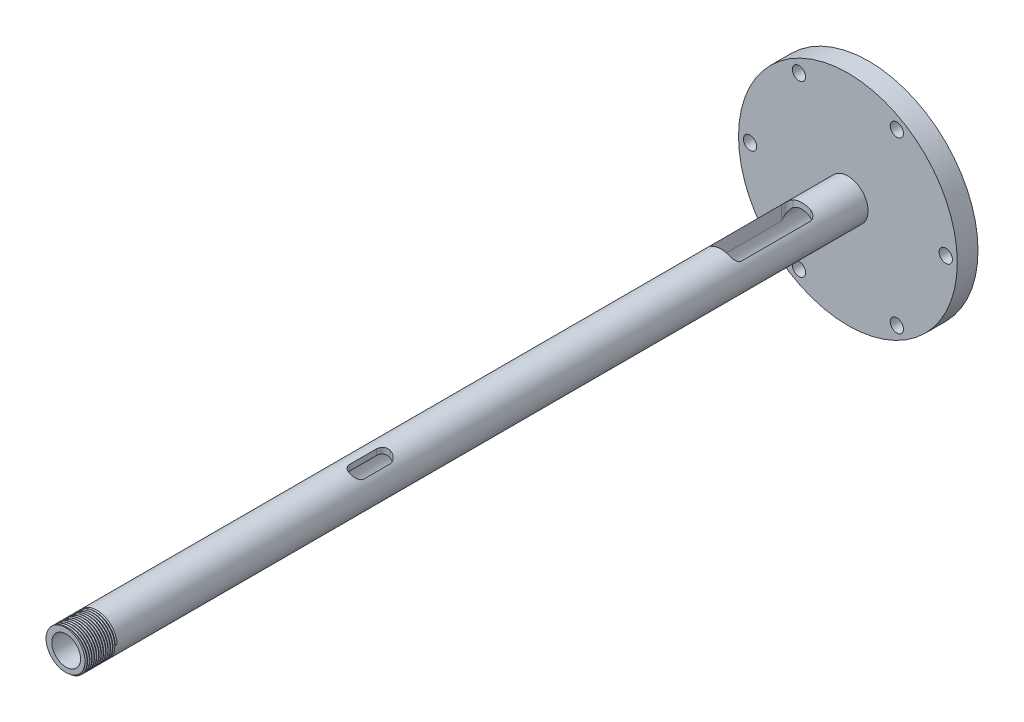
SolidWorks part; units mm, degrees
ref_plane "Front" through (0, 0, 0) normal (0, 0, 1) x (1, 0, 0)
ref_plane "Top" through (0, 0, 0) normal (0, 1, 0) x (1, 0, 0)
ref_plane "Right" through (0, 0, 0) normal (1, 0, 0) x (0, 0, -1)
sketch "Sketch1" plane through (0, 0, 0) normal (0, 0, 1) x (1, 0, 0)
  circle A0 centre (0, 0) radius 17.5
  circle A1 centre (0, 0) radius 12.5
  dimension "D1" = 35
  dimension "D2" = 25
extrude "Boss-Extrude1" add sketch "Sketch1" along normal blind 700
sketch "Sketch2" plane through (0, 0, 0) normal (0, 0, -1) x (-1, 0, 0)
  circle A0 centre (0, 0) radius 72.5
  circle A1 centre (0, 0) radius 12.5 construction
  circle A2 centre (0, 0) radius 12.5
  dimension "D1" = 145
extrude "Boss-Extrude2" add sketch "Sketch2" against normal blind 3
sketch "Sketch3" plane through (0, 0, 3) normal (0, 0, 1) x (1, 0, 0)
  circle A0 centre (0, 0) radius 95
  circle A1 centre (0, 0) radius 17.5 construction
  circle A2 centre (0, 0) radius 17.5
  dimension "D1" = 190
extrude "Boss-Extrude3" add sketch "Sketch3" along normal blind 18
sketch "Sketch4" plane through (0, 0, 3) normal (0, 0, -1) x (-1, 0, 0)
  line L0 (0, 0) -> (85, 0) construction
  circle A0 centre (0, 0) radius 85 construction
  circle A1 centre (85, 0) radius 5.75
  dimension "D1" = 170
  dimension "D2" = 11.5
extrude "Cut-Extrude1" cut sketch "Sketch4" against normal up to next
pattern_circular "CirPattern1" count 6 over 360 about axis through (0, 0, 21) along (0, 0, 1) of "Cut-Extrude1"
sketch "Sketch5" plane through (0, 0, 0) normal (0, 1, 0) x (1, 0, 0)
  line L0 (0, 0) -> (0, -61) construction
  line L1 (-12.5, -61) -> (12.5, -61)
  line L2 (-12.5, -61) -> (-12.5, -131)
  line L3 (-12.5, -131) -> (12.5, -131)
  line L4 (12.5, -61) -> (12.5, -131)
  line L5 (-12.5, -61) -> (12.5, -131) construction
  line L6 (-12.5, -131) -> (12.5, -61) construction
  line L7 (-17.5, -21) -> (17.5, -21) construction
  point P0 (0, -96)
  dimension "D1" = 25
  dimension "D2" = 40
  dimension "D3" = 70
extrude "Cut-Extrude2" cut sketch "Sketch5" along normal up to next
fillet "Fillet1" radius 5 4 edges at (-12.5, 6.1237, 131) (12.5, 6.1237, 131) (12.5, 6.1237, 61) (-12.5, 6.1237, 61)
sketch "Sketch7" plane through (0, 0, 0) normal (0, 1, 0) x (1, 0, 0)
  line L0 (-17.5, -700) -> (17.5, -700) construction
  line L1 (12.5, -460) -> (0.5, -460)
  line L2 (12.5, -460) -> (12.5, -425)
  line L3 (12.5, -425) -> (0.5, -425)
  line L4 (0.5, -460) -> (0.5, -425)
  line L5 (12.5, -460) -> (0.5, -425) construction
  line L6 (12.5, -425) -> (0.5, -460) construction
  line L7 (12.5, -126) -> (12.5, -66) construction
  point P4 (6.5, -442.5)
  dimension "D1" = 240
  dimension "D2" = 35
  dimension "D3" = 12
extrude "Cut-Extrude3" cut sketch "Sketch7" along normal up to next
fillet "Fillet2" radius 6 4 edges at (0.5, 14.9914, 460) (12.5, 6.1237, 460) (12.5, 6.1237, 425) (0.5, 14.9914, 425)
thread "Thread1" pitch 2 method cut profile "Thread Profile1" start angle 0, offset 2, length 27, pitch 2, diameter 35
ref_plane "Plane1" through (-17.5, 0, 702) normal (0, -1, 0) x (-1, 0, 0)
sketch "Thread Profile1" plane through (-17.5, 0, 702) normal (0, -1, 0) x (-1, 0, 0)
  line L0 (0, 0) -> (0, 2) construction
  line L11 (0, 0) -> (0, 1.75)
  line L12 (0, 1.75) -> (-1.0825, 1.125)
  line L13 (-1.0825, 1.125) -> (-1.0825, 0.625)
  line L15 (-1.0825, 0.625) -> (0, 0)
  line L17 (-1.0825, 0.875) -> (0, 0.875) construction
  point P2 (0, 0)
  dimension "Pitch" = 2
  dimension "Profile_Angle" = 60
  dimension "Profile_Land" = 0.5
  dimension "Profile_Height" = 1.0825
